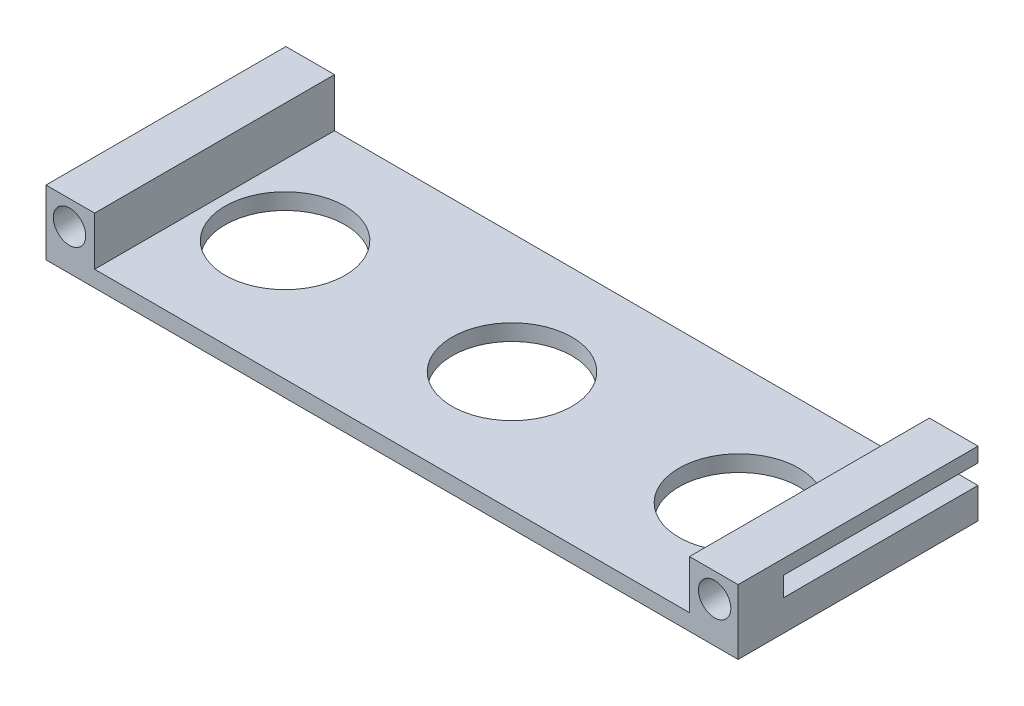
SolidWorks part; units mm, degrees
ref_plane "Front Plane" through (0, 0, 0) normal (0, 0, 1) x (1, 0, 0)
ref_plane "Top Plane" through (0, 0, 0) normal (0, 1, 0) x (1, 0, 0)
ref_plane "Right Plane" through (0, 0, 0) normal (1, 0, 0) x (0, 0, -1)
sketch "Sketch1" plane through (0, 0, 0) normal (0, 0, 1) x (1, 0, 0)
  line L0 (0, 68.3117) -> (0, -87.0424) construction
  line L1 (-42.7, 0) -> (42.7, 0)
  line L2 (42.7, 0) -> (42.7, 2)
  line L9 (42.7, 2) -> (-42.7, 2)
  line L16 (-42.7, 2) -> (-42.7, 0)
  dimension "D1" = 85.4
  dimension "D6" = 2
extrude "Boss-Extrude1" add sketch "Sketch1" along normal blind 29.6
sketch "Sketch2" plane through (0, 0, 0) normal (0, -1, 0) x (1, 0, 0)
  line L0 (-42.7, 14.8) -> (42.7, 14.8) construction
  line L1 (-42.7, 29.6) -> (-42.7, 0) construction
  line L2 (42.7, 29.6) -> (42.7, 0) construction
  line L3 (0, 0) -> (0, 29.6) construction
  line L4 (-42.7, 29.6) -> (42.7, 29.6) construction
  circle A0 centre (-28, 14.8) radius 7.4
  circle A1 centre (0, 14.8) radius 7.4
  circle A2 centre (28, 14.8) radius 7.4
  dimension "D1" = 14.8
  dimension "D2" = 28
extrude "Cut-Extrude1" cut sketch "Sketch2" against normal through all
sketch "Sketch4" plane through (0, 0, 0) normal (0, 0, -1) x (-1, 0, 0)
  line L0 (42.7, 2) -> (42.7, 3.8)
  line L1 (42.7, 3.8) -> (38.3, 3.8)
  line L2 (38.3, 3.8) -> (38.3, 6.2)
  line L3 (38.3, 6.2) -> (42.7, 6.2)
  line L4 (42.7, 6.2) -> (42.7, 8)
  line L5 (42.7, 8) -> (36.7, 8)
  line L6 (36.7, 8) -> (36.7, 2)
  line L7 (-42.7, 2) -> (42.7, 2) construction
  line L8 (0, 25.855) -> (0, -15.3286) construction
  line L9 (36.7, 2) -> (42.7, 2)
  line L10 (-36.7, 2) -> (-42.7, 2)
  line L11 (-36.7, 8) -> (-36.7, 2)
  line L12 (-42.7, 8) -> (-36.7, 8)
  line L13 (-42.7, 6.2) -> (-42.7, 8)
  line L14 (-38.3, 6.2) -> (-42.7, 6.2)
  line L15 (-38.3, 3.8) -> (-38.3, 6.2)
  line L16 (-42.7, 3.8) -> (-38.3, 3.8)
  line L17 (-42.7, 2) -> (-42.7, 3.8)
  line L18 (36.7, 5) -> (46.0116, 5) construction
  dimension "D1" = 6
  dimension "D2" = 6
  dimension "D3" = 2.4
  dimension "D4" = 4.4
extrude "Boss-Extrude2" add sketch "Sketch4" against normal blind 24
sketch "Sketch5" plane through (0, 0, 29.6) normal (0, 0, 1) x (1, 0, 0)
  line L0 (0, -28.6923) -> (0, 18.1076) construction
  line L10 (42.7, 2) -> (36.7, 2)
  line L11 (-42.7, 8) -> (-36.7, 8)
  line L12 (-42.7, 8) -> (-42.7, 2)
  line L13 (-42.7, 2) -> (-36.7, 2)
  line L14 (-36.7, 8) -> (-36.7, 2)
  line L15 (36.7, 8) -> (36.7, 2)
  line L16 (42.7, 8) -> (36.7, 8)
  line L17 (42.7, 8) -> (42.7, 2)
  point P4 (0, -5.2923)
extrude "Boss-Extrude3" add sketch "Sketch5" against normal up to surface (5.6 mm away) up to face at (-40.1, 5, 24)
sketch "Sketch6" plane through (0, 0, 29.6) normal (0, 0, 1) x (1, 0, 0)
  line L0 (0, 21.7532) -> (0, -12.1597) construction
  line L1 (-42.7, 8) -> (-42.7, 0) construction
  line L3 (-36.7, 8) -> (-42.7, 8) construction
  circle A0 centre (-39.8, 5) radius 2
  circle A1 centre (39.8, 5) radius 2
  dimension "D1" = 4
  dimension "D2" = 2.9
  dimension "D3" = 3
extrude "Cut-Extrude2" cut sketch "Sketch6" against normal blind 3.2
